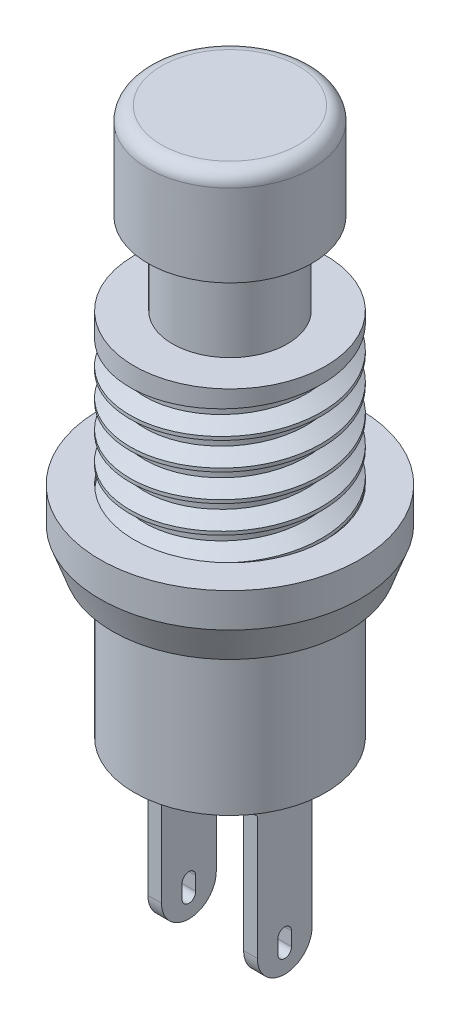
SolidWorks part; units mm, degrees
ref_plane "Спереди" through (0, 0, 0) normal (0, 0, 1) x (1, 0, 0)
ref_plane "Сверху" through (0, 0, 0) normal (0, 1, 0) x (1, 0, 0)
ref_plane "Справа" through (0, 0, 0) normal (1, 0, 0) x (0, 0, -1)
sketch "Эскиз1" plane through (0, 0, 0) normal (0, 0, 1) x (1, 0, 0)
  line L0 (0, 14.5) -> (3, 14.5)
  line L1 (3, 14.5) -> (3, 11)
  line L2 (3, 11) -> (2.1, 11)
  line L3 (2.1, 11) -> (2.1, 8)
  line L4 (2.1, 8) -> (3.5, 8)
  line L5 (3.5, 8) -> (3.5, 2.5)
  line L6 (3.5, 2.5) -> (4.75, 2.5)
  line L7 (4.75, 2.5) -> (4.75, 1.25)
  line L8 (4.75, 1.25) -> (4.295, 0)
  line L9 (4.295, 0) -> (3.5, 0)
  line L10 (3.5, 0) -> (3.5, -5.5)
  line L11 (3.5, -5.5) -> (0, -5.5)
  line L12 (0, -5.5) -> (0, 14.5)
  line L13 (0, -263.7685) -> (0, 13178.4055) construction
  point P15 (4.75, 1.875)
  point P17 (2.8, 8)
  point P18 (0, 0)
  point P19 (0, 0)
  point P20 (0, 0)
  dimension "D1" = 6
  dimension "D2" = 4.2
  dimension "D3" = 7
  dimension "D4" = 9.5
  dimension "D5" = 7
  dimension "D6" = 5.5
  dimension "D7" = 2.5
  dimension "D8" = 20
  dimension "D9" = 3.5
  dimension "D10" = 3
  dimension "D11" = 20
  dimension "D12" = 1.25
revolve "Повернуть1" add sketch "Эскиз1" angle 360 about L13
fillet "Скругление1" radius 0.5 1 edges at (0, 14.5, -3)
thread "Резьба1" pitch 1 method cut profile "Профиль резьбы1" start angle 0, offset 0, length 0, pitch 1, diameter 7
ref_plane "Плоскость1" through (-3.5, 8, 0) normal (0, 0, 1) x (-1, 0, 0)
sketch "Профиль резьбы1" plane through (-3.5, 8, 0) normal (0, 0, 1) x (-1, 0, 0)
  line L0 (0, 0) -> (0, 1) construction
  line L11 (0, 0) -> (0, 0.875)
  line L12 (0, 0.875) -> (-0.5413, 0.5625)
  line L13 (-0.5413, 0.5625) -> (-0.5413, 0.3125)
  line L15 (-0.5413, 0.3125) -> (0, 0)
  line L17 (-0.5413, 0.4375) -> (0, 0.4375) construction
  point P2 (0, 0)
  dimension "Pitch" = 1
  dimension "Profile_Angle" = 60
  dimension "Profile_Land" = 0.25
  dimension "Profile_Height" = 0.5413
sketch "Эскиз7" plane through (0, -5.5, 0) normal (0, -1, 0) x (1, 0, 0)
  line L0 (0, -1000) -> (0, 49000) construction
  line L1 (-1000, 0) -> (49000, 0) construction
  line L2 (2, -2) -> (1.5, -2)
  line L3 (-2, 2) -> (-1.5, 2)
  line L4 (-2, 2) -> (-2, -2)
  line L5 (-2, -2) -> (-1.5, -2)
  line L6 (-1.5, 2) -> (-1.5, -2)
  line L7 (1.5, 2) -> (1.5, -2)
  line L8 (2, 2) -> (1.5, 2)
  line L9 (2, 2) -> (2, -2)
  point P9 (-2, 0)
  dimension "D1" = 4
  dimension "D2" = 4
  dimension "D3" = 0.5
extrude "Бобышка-Вытянуть1" add sketch "Эскиз7" along normal blind 6.5
sketch "Эскиз8" plane through (-2, 0, 0) normal (-1, 0, 0) x (0, 0, 1)
  line L0 (0, -1012) -> (0, -12.0691) construction
  line L1 (2, -12) -> (-2, -12) construction
  line L2 (1, -6.5) -> (2, -5.5)
  line L4 (-1, -6.5) -> (-1, -11)
  line L6 (1, -6.5) -> (1, -11)
  line L8 (-2, -5.5) -> (-1, -6.5)
  line L9 (-2, -12) -> (-2, -5.5) construction
  line L10 (0, -11.25) -> (0, -10.75) construction
  line L11 (-0.25, -11.25) -> (-0.25, -10.75)
  line L12 (0.25, -11.25) -> (0.25, -10.75)
  line L13 (2, -5.5) -> (2, -12)
  line L14 (2, -12) -> (0.0421, -12)
  line L15 (-0.0494, -12) -> (-2, -12)
  line L16 (-2, -12) -> (-2, -5.5)
  line L17 (0, -12) -> (0, 48988) construction
  line L19 (-0.0494, -11.9988) -> (-0.0494, -12)
  line L21 (0.0421, -11.9991) -> (0.0421, -12)
  arc A0 (-1, -11) -> (-0.0494, -11.9988) centre (0, -11) ccw
  arc A1 (-0.25, -11.25) -> (0.25, -11.25) centre (0, -11.25) ccw
  arc A2 (0.25, -10.75) -> (-0.25, -10.75) centre (0, -10.75) ccw
  arc A3 (0.0421, -11.9991) -> (1, -11) centre (0, -11) ccw
  point P5 (0, -12)
  point P18 (0, -11)
  dimension "D1" = 2
  dimension "D2" = 45
  dimension "D3" = 0.5
  dimension "D4" = 0.5
extrude "Вырез-Вытянуть1" cut sketch "Эскиз8" against normal up to surface (4 mm away) up to face at (2, -8.75, 0)
